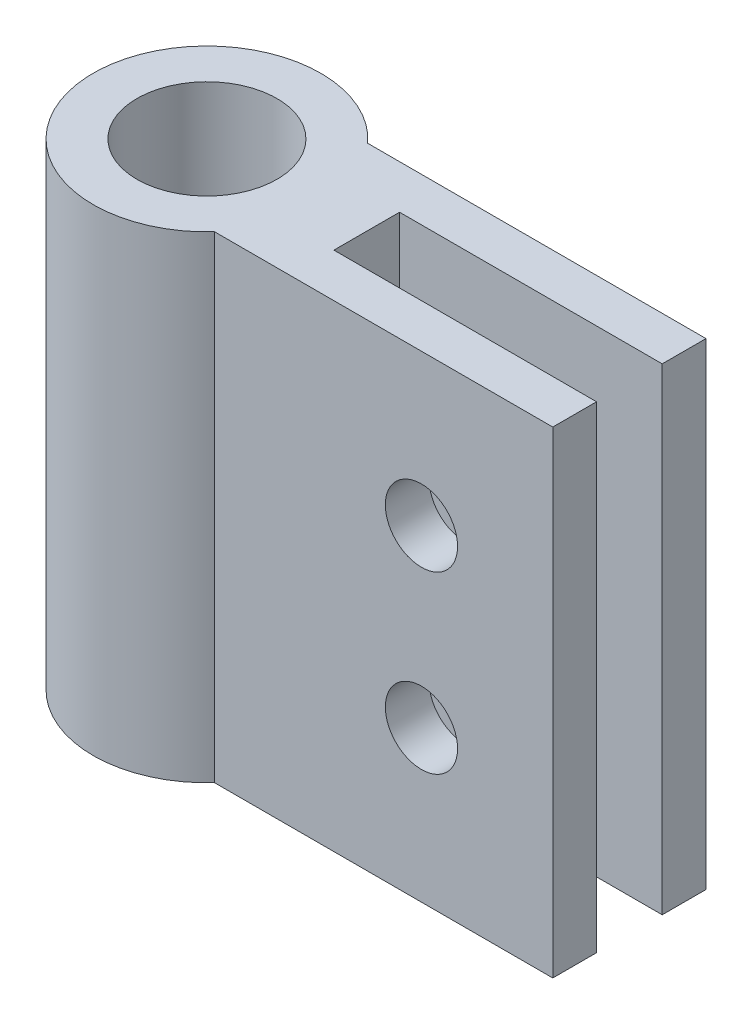
SolidWorks part; units mm, degrees
ref_plane "前视基准面" through (0, 0, 0) normal (0, 0, 1) x (1, 0, 0)
ref_plane "上视基准面" through (0, 0, 0) normal (0, 1, 0) x (1, 0, 0)
ref_plane "右视基准面" through (0, 0, 0) normal (1, 0, 0) x (0, 0, -1)
sketch "草图1" plane through (0, 0, 0) normal (0, 1, 0) x (1, 0, 0)
  circle A0 centre (0, 0) radius 3.2
  circle A1 centre (0, 0) radius 5.2
  dimension "D1" = 6.4
  dimension "D2" = 2
extrude "凸台-拉伸1" add sketch "草图1" along normal blind 21.8
sketch "草图2" plane through (0, 21.8, 0) normal (0, 1, 0) x (1, 0, 0)
  line L1 (19.3, -3.5) -> (3.3, -3.5)
  line L2 (19.3, -3.5) -> (19.3, 3.5)
  line L3 (19.3, 3.5) -> (3.3, 3.5)
  line L4 (3.3, -3.5) -> (3.3, 3.5)
  line L5 (19.3, -3.5) -> (3.3, 3.5) construction
  line L6 (19.3, 3.5) -> (3.3, -3.5) construction
  point P0 (11.3, 0)
  dimension "D1" = 11.3
  dimension "D2" = 16
  dimension "D3" = 7
extrude "凸台-拉伸2" add sketch "草图2" against normal up to surface (21.8 mm away) up to face at (0, 0, 5.2)
sketch "草图3" plane through (0, 21.8, 0) normal (0, 1, 0) x (1, 0, 0)
  line L0 (19.3, -3.5) -> (19.3, 3.5) construction
  line L1 (7.3, -1.5) -> (19.3, -1.5)
  line L2 (7.3, -1.5) -> (7.3, 1.5)
  line L3 (7.3, 1.5) -> (19.3, 1.5)
  line L4 (19.3, -1.5) -> (19.3, 1.5)
  line L5 (7.3, -1.5) -> (19.3, 1.5) construction
  line L6 (7.3, 1.5) -> (19.3, -1.5) construction
  point P0 (13.3, 0)
  dimension "D1" = 3
  dimension "D2" = 12
extrude "切除-拉伸1" cut sketch "草图3" against normal blind 22
sketch "草图4" plane through (0, 0, 3.5) normal (0, 0, 1) x (1, 0, 0)
  line L0 (7.3, 0) -> (7.3, 21.8) construction
  line L1 (7.3, 0) -> (7.3, 21.8) construction
  line L2 (3.8458, 21.8) -> (19.3, 21.8) construction
  circle A0 centre (13.3, 14.9) radius 1.65
  circle A1 centre (13.3, 6.9) radius 1.65
  dimension "D1" = 3.3
  dimension "D2" = 3.3
  dimension "D3" = 6.9
  dimension "D4" = 6
  dimension "D5" = 8
extrude "切除-拉伸2" cut sketch "草图4" against normal blind 22
